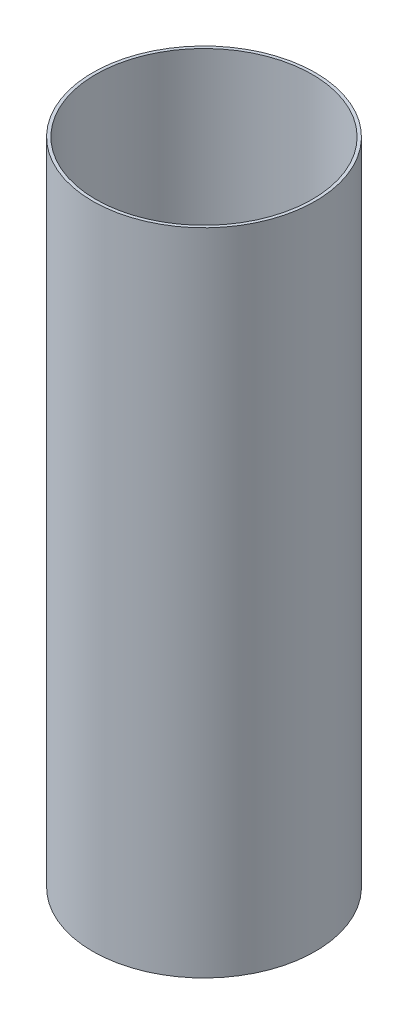
SolidWorks part; units mm, degrees
material "Acrylic (Medium-high impact)"
ref_plane "Front Plane" through (0, 0, 0) normal (0, 0, 1) x (1, 0, 0)
ref_plane "Top Plane" through (0, 0, 0) normal (0, 1, 0) x (1, 0, 0)
ref_plane "Right Plane" through (0, 0, 0) normal (1, 0, 0) x (0, 0, -1)
sketch "Sketch2" plane through (0, 0, 0) normal (0, 1, 0) x (1, 0, 0)
  circle A0 centre (0, 0) radius 76.2
  circle A1 centre (0, 0) radius 78.359
  dimension "D1" = 152.4
  dimension "D2" = 156.718
extrude "Boss-Extrude1" add sketch "Sketch2" along normal blind 457.2
